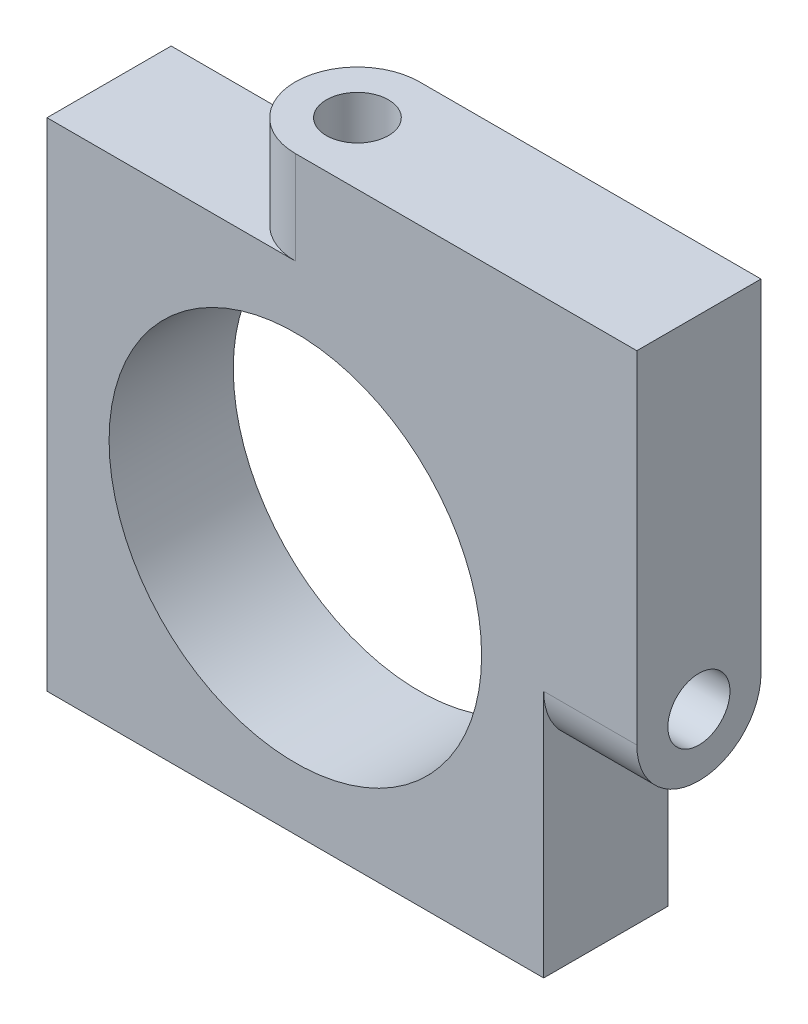
SolidWorks part; units mm, degrees
ref_plane "Front Plane" through (0, 0, 0) normal (0, 0, 1) x (1, 0, 0)
ref_plane "Top Plane" through (0, 0, 0) normal (0, 1, 0) x (1, 0, 0)
ref_plane "Right Plane" through (0, 0, 0) normal (1, 0, 0) x (0, 0, -1)
sketch "Sketch2" plane through (0, 0, 0) normal (0, 0, 1) x (1, 0, 0)
  line L1 (0, 0) -> (101.6, 0)
  line L2 (0, 0) -> (0, 101.6)
  line L3 (0, 101.6) -> (101.6, 101.6)
  line L4 (101.6, 0) -> (101.6, 101.6)
  circle A0 centre (50.8, 50.8) radius 38.1
  dimension "D3" = 76.2
  dimension "D1" = 101.6
  dimension "D2" = 101.6
  dimension "D4" = 50.8
  dimension "D5" = 50.8
extrude "Boss-Extrude1" add sketch "Sketch2" along normal blind 25.4
sketch "Sketch3" plane through (0, 101.6, 0) normal (0, 1, 0) x (1, 0, 0)
  line L0 (101.6, -25.4) -> (0, -25.4) construction
  line L1 (101.6, 0) -> (50.8, 0)
  line L2 (101.6, 0) -> (101.6, -25.4)
  line L3 (101.6, -25.4) -> (50.8, -25.4)
  line L4 (50.8, 0) -> (50.8, -25.4)
  arc A0 (50.8, 0) -> (50.8, -25.4) centre (50.8, -12.7) ccw
  circle A1 centre (50.8, -12.7) radius 6.35
  line M1 (101.6, 0) -> (0, 0)
  line M3 (0, -25.4) -> (101.6, -25.4)
  line M4 (101.6, -25.4) -> (101.6, 0)
  dimension "D1" = 12.7
  dimension "D2" = 12.7
  dimension "D3" = 25.4
extrude "Boss-Extrude2" add sketch "Sketch3" along normal blind 19.05 contours A1 L4 A0 | A1 L4 M3 M4 M1 region at (77.3721, 101.6, 12.7) region at (50.516, 101.6, 3.175)
sketch "Sketch4" plane through (101.6, 0, 0) normal (1, 0, 0) x (0, 0, -1)
  line L0 (0, 0) -> (0, 120.65) construction
  line L1 (-25.4, 120.65) -> (0, 120.65)
  line L2 (-25.4, 120.65) -> (-25.4, 50.8)
  line L3 (-25.4, 50.8) -> (0, 50.8)
  line L4 (0, 120.65) -> (0, 50.8)
  arc A0 (-25.4, 50.8) -> (0, 50.8) centre (-12.7, 50.8) ccw
  circle A1 centre (-12.7, 50.8) radius 6.35
  line M2 (0, 0) -> (0, 120.65)
  line M3 (0, 120.65) -> (-25.4, 120.65)
  line M4 (-25.4, 120.65) -> (-25.4, 0)
  dimension "D2" = 12.7
  dimension "D1" = 69.85
extrude "Boss-Extrude3" add sketch "Sketch4" along normal blind 19.05 contours A1 L3 A0 | A1 L3 M2 M3 M4 region at (101.6, 86.9182, 12.7) region at (101.6, 50.516, 22.225)
